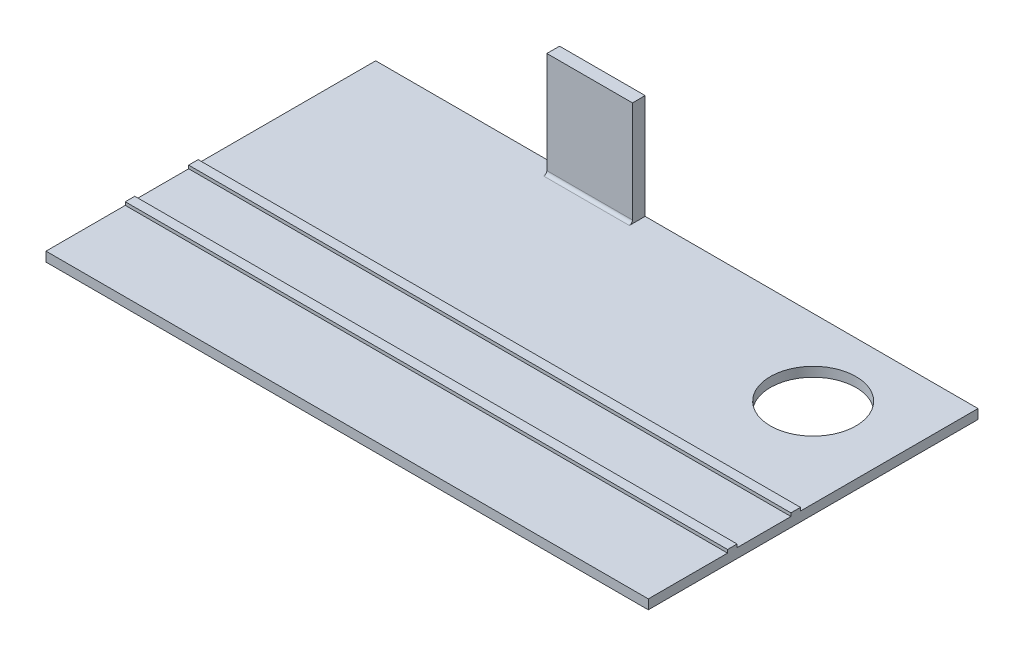
SolidWorks part; units mm, degrees
ref_plane "Piano frontale" through (0, 0, 0) normal (0, 0, 1) x (1, 0, 0)
ref_plane "Piano superiore" through (0, 0, 0) normal (0, 1, 0) x (1, 0, 0)
ref_plane "Piano destro" through (0, 0, 0) normal (1, 0, 0) x (0, 0, -1)
sketch "Schizzo1" plane through (0, 0, 0) normal (0, 0, 1) x (1, 0, 0)
  line L1 (0, 0) -> (27, 0)
  line L2 (0, 0) -> (0, -36)
  line L3 (0, -36) -> (27, -36)
  line L4 (27, 0) -> (27, -36)
  dimension "D1" = 27
  dimension "D2" = 36
extrude "Estrusione-Estrusione1" add sketch "Schizzo1" along normal blind 4
sketch "Schizzo3" plane through (0, 0, 4) normal (0, 0, 1) x (1, 0, 0)
  line L0 (27, -36) -> (27, 0) construction
  line L1 (0, -36) -> (27, -36)
  line L2 (0, -36) -> (0, -33)
  line L3 (0, -33) -> (27, -33)
  line L4 (27, -36) -> (27, -33)
  dimension "D1" = 3
extrude "Estrusione-Estrusione2" add sketch "Schizzo3" along normal blind 100
fillet "Raccordo1" radius 1 1 edges at (13.5, -33, 4)
sketch "Schizzo5" plane through (27, 0, 0) normal (1, 0, 0) x (0, 0, -1)
  line L0 (0, -36) -> (0, 0) construction
  line L1 (-104, -36) -> (0, -36)
  line L2 (-104, -36) -> (-104, -33)
  line L3 (-104, -33) -> (0, -33)
  line L4 (0, -36) -> (0, -33)
  line L9 (-104, -33) -> (-5, -33) construction
extrude "Estrusione-Estrusione3" add sketch "Schizzo5" along normal blind 170 and the other way blind 150
sketch "Schizzo6" plane through (-123, 0, 0) normal (-1, 0, 0) x (0, 0, 1)
  line L0 (56, -33) -> (56, -32.5)
  line L1 (0, -33) -> (104, -33) construction
  line L3 (56, -32.5) -> (56, -32)
  line L4 (56, -32) -> (59, -32)
  line L5 (59, -32) -> (59, -32.5)
  line L6 (76, -33) -> (79, -33)
  line L7 (59, -32.5) -> (59, -33)
  line L8 (76, -33) -> (76, -32)
  line L9 (76, -32) -> (79, -32)
  line L10 (79, -33) -> (79, -32)
  line M11 (104, -33) -> (0, -33)
  dimension "D1" = 1
  dimension "D2" = 3
  dimension "D3" = 3
  dimension "D4" = 1
  dimension "D5" = 17
  dimension "D6" = 25
extrude "Estrusione-Estrusione4" add sketch "Schizzo6" against normal blind 320 contours L7 L5 L4 L3 L0 M11 | L10 L9 L8 M11 region at (-123, -32.5, 77.5) region at (-123, -32.5, 57.5)
sketch "Schizzo7" plane through (0, -33, 0) normal (0, 1, 0) x (1, 0, 0)
  line L0 (197, -104) -> (-123, -104) construction
  line L1 (-123, 0) -> (-58, 0)
  line L2 (-123, 0) -> (-123, -104)
  line L3 (-123, -104) -> (-58, -104)
  line L4 (-58, 0) -> (-58, -104)
  line L6 (197, 0) -> (132, 0)
  line L7 (197, 0) -> (197, -104)
  line L8 (197, -104) -> (132, -104)
  line L9 (132, 0) -> (132, -104)
  dimension "D1" = 65
extrude "Taglio-Estrusione1" cut sketch "Schizzo7" against normal blind 10 and the other way blind 10
sketch "Schizzo8" plane through (0, -33, 0) normal (0, 1, 0) x (1, 0, 0)
  line L0 (132, 0) -> (132, -56) construction
  line L1 (27, 0) -> (132, 0) construction
  circle A0 centre (104, -24) radius 13.5
  dimension "D1" = 27
  dimension "D2" = 28
  dimension "D3" = 24
extrude "Taglio-Estrusione2" cut sketch "Schizzo8" against normal blind 10
